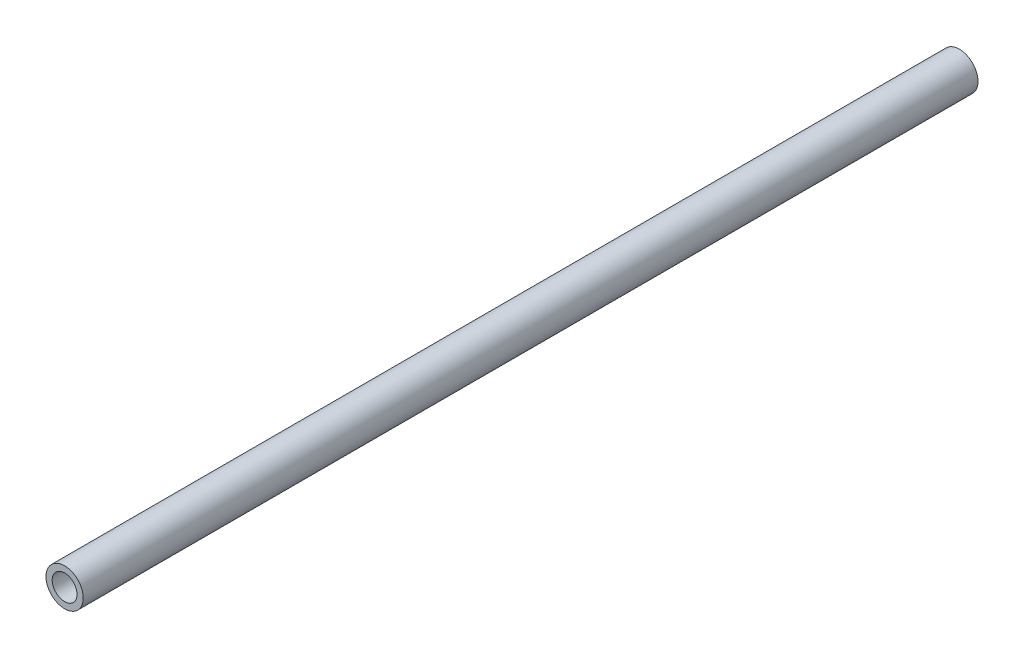
SolidWorks part; units mm, degrees
ref_plane "Front Plane" through (0, 0, 0) normal (0, 0, 1) x (1, 0, 0)
ref_plane "Top Plane" through (0, 0, 0) normal (0, 1, 0) x (1, 0, 0)
ref_plane "Right Plane" through (0, 0, 0) normal (1, 0, 0) x (0, 0, -1)
sketch "Sketch1" plane through (0, 0, 0) normal (0, 0, 1) x (1, 0, 0)
  circle A0 centre (0, 0) radius 6.35
  circle A1 centre (0, 0) radius 9.525
  dimension "D1" = 12.7
  dimension "D2" = 19.05
extrude "Boss-Extrude1" add sketch "Sketch1" along normal blind 457.2
equation "\"span\" = 48"
equation "\"wing_chord\"= 9"
equation "\"fuse_len\"= 15"
equation "\"fuse_height\"= 5"
equation "\"fuse_wid\"= 5"
equation "\"foam_t\"= 0.1875"
equation "\"main_spar_len\"= 36"
equation "\"x_fuse_to_wing\"= 3"
equation "\"x_cg_from_le\"= 2.25"
equation "\"boom_len\"= 36"
equation "\"D1@Boss-Extrude1\"= \"boom_len\"/2"
